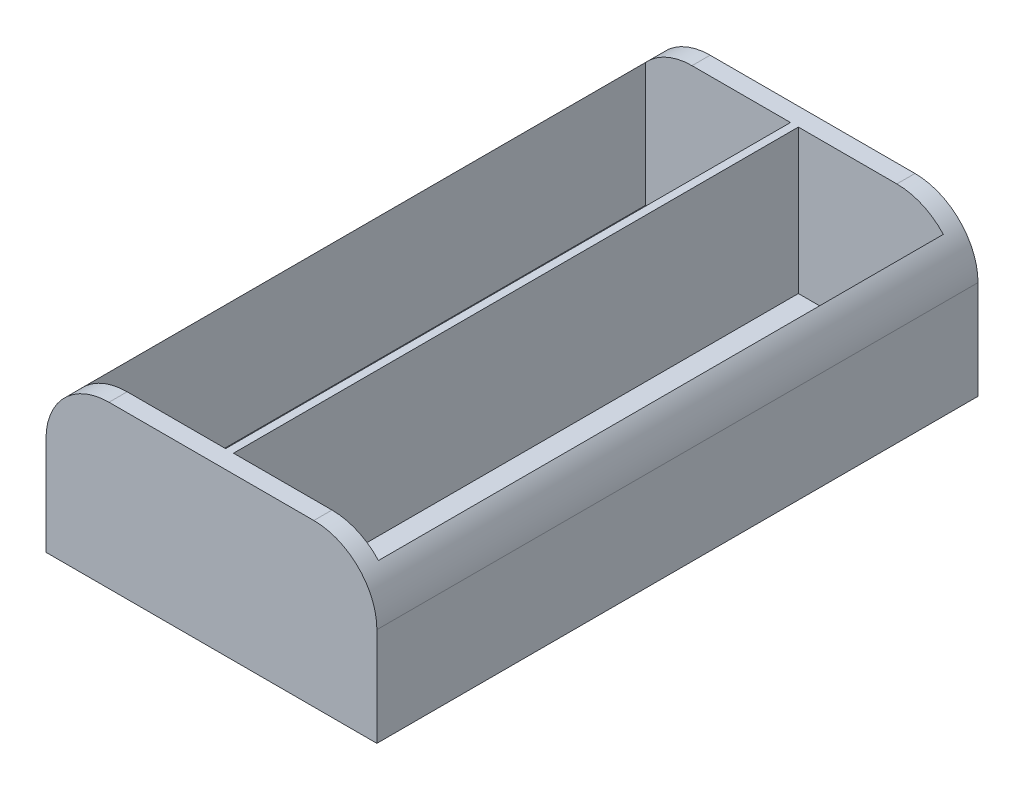
SolidWorks part; units mm, degrees
material "ABS"
ref_plane "Front" through (0, 0, 0) normal (0, 0, 1) x (1, 0, 0)
ref_plane "Top" through (0, 0, 0) normal (0, 1, 0) x (1, 0, 0)
ref_plane "Right" through (0, 0, 0) normal (1, 0, 0) x (0, 0, -1)
sketch "Эскиз1" plane through (0, 0, 0) normal (0, 1, 0) x (1, 0, 0)
  line L0 (21, -38.15) -> (21, 38.15)
  line L1 (21, -38.15) -> (-21, -38.15)
  line L2 (21, 38.15) -> (-21, 38.15)
  line L3 (-21, -38.15) -> (-21, 38.15)
  line L4 (21, -38.15) -> (-21, 38.15) construction
  line L5 (21, 38.15) -> (-21, -38.15) construction
  circle A0 centre (0, 0) radius 10.5 construction
  circle A1 centre (-10.5, 0) radius 1.5
  circle A2 centre (10.5, 0) radius 1.5
  point P1 (0, 0)
  dimension "D3" = 21
  dimension "D1" = 42
  dimension "D2" = 76.3
extrude "Бобышка-Вытянуть1" add sketch "Эскиз1" along normal blind 20.5 contours L1 L3 L2 L0
fillet "Скругление1" radius 8 2 edges at (-21, 20.5, 0) (21, 20.5, 0)
shell "Оболочка1" thickness 2.3
sketch "Эскиз3" plane through (0, 0, 0) normal (0, 1, 0) x (1, 0, 0)
  line L0 (18.9, -35.85) -> (18.9, 35.85)
  line L1 (18.9, -35.85) -> (-18.9, -35.85)
  line L2 (18.9, 35.85) -> (-18.9, 35.85)
  line L3 (-18.9, -35.85) -> (-18.9, 35.85)
  line L4 (18.9, -35.85) -> (-18.9, 35.85) construction
  line L5 (18.9, 35.85) -> (-18.9, -35.85) construction
  point P1 (0, 0)
  dimension "D1" = 37.8
  dimension "D2" = 71.7
extrude "Вырез-Вытянуть1" cut sketch "Эскиз3" along normal through all from offset 2.2
extrude "Вырез-Вытянуть2" cut sketch "Эскиз1<3>" along normal through all contours A2 | A1
sketch "Эскиз1<3>" plane through (0, 0, 0) normal (0, 1, 0) x (1, 0, 0) same geometry as "Эскиз1"
sketch "Эскиз4" plane through (0, 0, 0) normal (0, 1, 0) x (1, 0, 0)
  line L0 (0.5, -38.15) -> (0.5, 38.15)
  line L1 (0.5, -38.15) -> (-0.5, -38.15)
  line L2 (0.5, 38.15) -> (-0.5, 38.15)
  line L3 (-0.5, -38.15) -> (-0.5, 38.15)
  line L4 (0.5, -38.15) -> (-0.5, 38.15) construction
  line L5 (0.5, 38.15) -> (-0.5, -38.15) construction
  point P1 (0, 0)
  dimension "D1" = 1
extrude "Бобышка-Вытянуть2" add sketch "Эскиз4" along normal blind 20.5
chamfer "Chamfer1" distance 1.3 angle 45 2 edges at (10.5, 2.2, -1.5) (-10.5, 2.2, -1.5)
